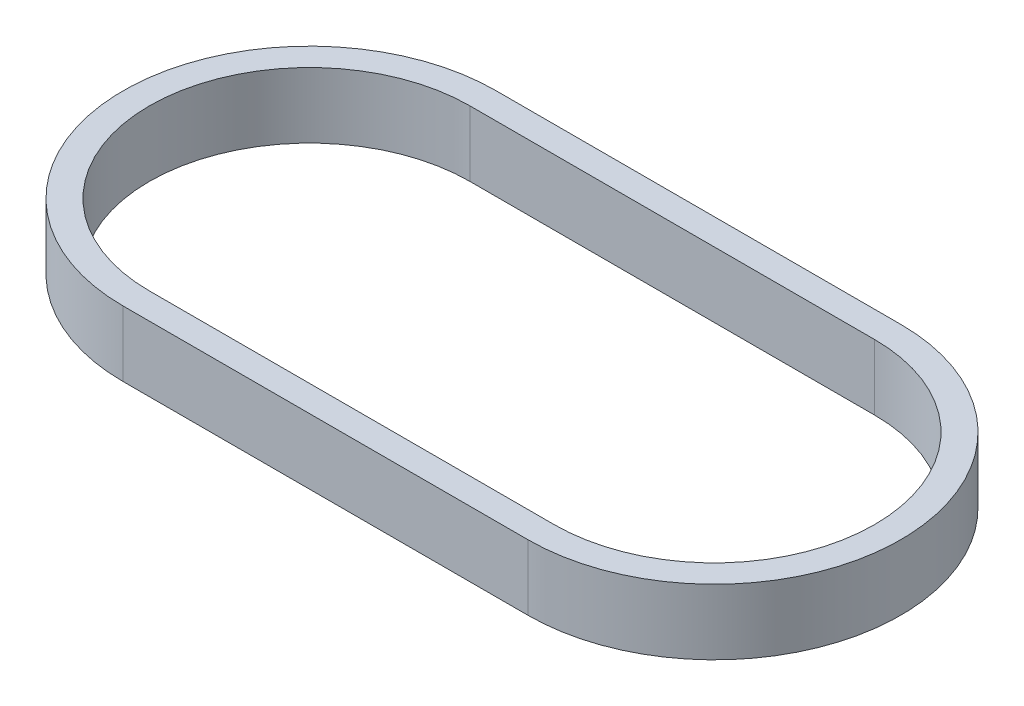
SolidWorks part; units mm, degrees
ref_plane "Front" through (0, 0, 0) normal (0, 0, 1) x (1, 0, 0)
ref_plane "Top" through (0, 0, 0) normal (0, 1, 0) x (1, 0, 0)
ref_plane "Right" through (0, 0, 0) normal (1, 0, 0) x (0, 0, -1)
sketch "Sketch1" plane through (0, 0, 0) normal (0, 1, 0) x (1, 0, 0)
  line L0 (0, 36.1721) -> (78.5207, 36.1721)
  line L1 (0, -36.1721) -> (78.5207, -36.1721)
  line L2 (0, 31.0921) -> (78.5207, 31.0921)
  line L3 (0, -31.0921) -> (78.5207, -31.0921)
  arc A0 (0, 36.1721) -> (0, -36.1721) centre (0, 0) ccw
  arc A1 (78.5207, -36.1721) -> (78.5207, 36.1721) centre (78.5207, 0) ccw
  arc A2 (78.5207, -31.0921) -> (78.5207, 31.0921) centre (78.5207, 0) ccw
  arc A3 (0, 31.0921) -> (0, -31.0921) centre (0, 0) ccw
  circle A6 centre (78.5207, 0) radius 32.4639 construction
  dimension "D1" = 72.3443
  dimension "D2" = 5.08
extrude "Boss-Extrude1" add sketch "Sketch1" along normal blind 12.7
